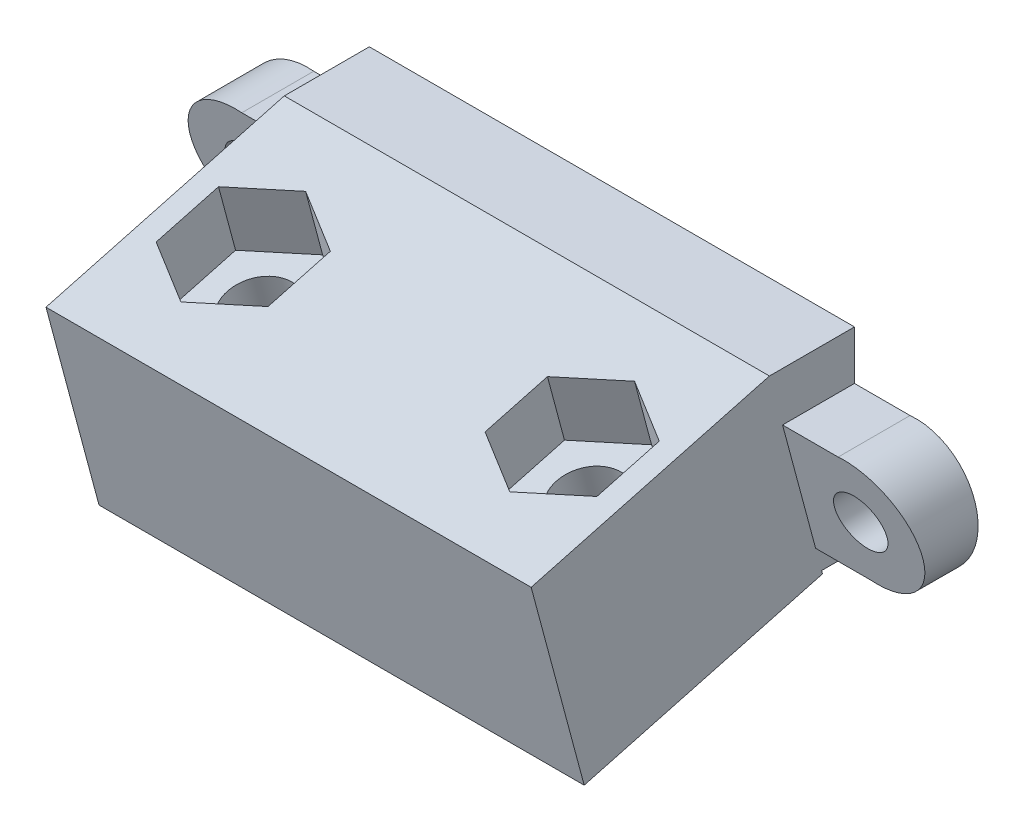
SolidWorks part; units mm, degrees
ref_plane "Front Plane" through (0, 0, 0) normal (0, 0, 1) x (1, 0, 0)
ref_plane "Top Plane" through (0, 0, 0) normal (0, 1, 0) x (1, 0, 0)
ref_plane "Right Plane" through (0, 0, 0) normal (1, 0, 0) x (0, 0, -1)
sketch "Sketch1" plane through (0, 0, 0) normal (0, 0, 1) x (1, 0, 0)
  line L0 (0, 2.5231) -> (3.38, 2.5231) construction
  line L1 (-32.88, 2.5231) -> (-29.5, 2.5231) construction
  line L2 (-32.88, 10.0231) -> (-29.5, 10.0231)
  line L3 (-29.5, 10.0231) -> (-29.5, 13)
  line L4 (-29.5, 13) -> (0, 13)
  line L5 (0, 13) -> (0, 10.0231)
  line L6 (0, 10.0231) -> (3.38, 10.0231)
  line L7 (3.38, 2.5231) -> (0, 2.5231)
  line L8 (0, 2.5231) -> (0, 1.1677)
  line L9 (0, 1.1677) -> (-29.5, 1.1677)
  line L10 (-29.5, 1.1677) -> (-29.5, 2.5231)
  line L11 (-29.5, 2.5231) -> (-32.88, 2.5231)
  line L12 (10.8, 1.1677) -> (-39.2, 1.1677) construction
  circle A0 centre (-33.25, 6.2731) radius 1.6
  circle A1 centre (3.75, 6.2731) radius 1.6
  arc A2 (3.38, 10.0231) -> (3.38, 2.5231) centre (3.75, 6.2731) cw
  arc A3 (-32.88, 10.0231) -> (-32.88, 2.5231) centre (-33.25, 6.2731) ccw
  circle A4 centre (-33.25, 6.2731) radius 1.6 construction
  circle A5 centre (3.75, 6.2731) radius 1.6 construction
  dimension "D1" = 0
extrude "Boss-Extrude1" add sketch "Sketch1" along normal blind 2
sketch "Sketch3" plane through (0, 1.3876, 0.3718) normal (0, 0.9659, 0.2588) x (1, 0, 0)
  line L0 (-29.5, -1.6296) -> (0, -1.6296) construction
  line L1 (0, -1.6296) -> (-29.5, -1.6296)
  line L2 (0, -1.6296) -> (0, -16.6296)
  line L3 (0, -16.6296) -> (-29.5, -16.6296)
  line L4 (-29.5, -1.6296) -> (-29.5, -16.6296)
  line L5 (0, -1.6296) -> (-29.5, -16.6296) construction
  line L6 (0, -16.6296) -> (-29.5, -1.6296) construction
  line L7 (-29.5, -1.2788) -> (-29.5, -1.6296) construction
  circle A0 centre (-4.75, -9.1296) radius 2
  circle A1 centre (-24.75, -9.1296) radius 2
  point P4 (-14.75, -9.1296)
  dimension "D4" = 4
  dimension "D7" = 4
  dimension "D1" = 15
  dimension "D2" = 20
  dimension "D3" = 4.75
  dimension "D5" = 7.5
  dimension "D6" = 7.5
extrude "Boss-Extrude2" add sketch "Sketch3" along normal up to vertex (11.6382 mm away) separate body up to point (-29.5, 13, 2)
extrude "Boss-Extrude3" add sketch "Sketch1<2>" along normal up to surface (3.368 mm away) up to face at (-14.75, 6.5866, 3.452)
sketch "Sketch1<2>" plane through (0, 0, 0) normal (0, 0, 1) x (1, 0, 0) same geometry as "Sketch1"
extrude "Boss-Extrude4" add sketch "Sketch3<2>" along normal up to vertex (12.4587 mm away) up to point (-29.5, 13, 5.1704)
sketch "Sketch3<2>" plane through (0, 1.3876, 0.3718) normal (0, 0.9659, 0.2588) x (1, 0, 0) same geometry as "Sketch3"
sketch "Sketch4" plane through (0, 13.4218, 3.5964) normal (0, 0.9659, 0.2588) x (1, 0, 0)
  line L1 (-1.35, -11.0926) -> (-1.35, -7.1666)
  line L2 (-1.35, -7.1666) -> (-4.75, -5.2036)
  line L3 (-4.75, -5.2036) -> (-8.15, -7.1666)
  line L4 (-8.15, -7.1666) -> (-8.15, -11.0926)
  line L5 (-8.15, -11.0926) -> (-4.75, -13.0556)
  line L6 (-4.75, -13.0556) -> (-1.35, -11.0926)
  line L7 (-21.35, -7.1666) -> (-24.75, -5.2036)
  line L8 (-24.75, -5.2036) -> (-28.15, -7.1666)
  line L9 (-28.15, -7.1666) -> (-28.15, -11.0926)
  line L10 (-28.15, -11.0926) -> (-24.75, -13.0556)
  line L11 (-24.75, -13.0556) -> (-21.35, -11.0926)
  line L12 (-21.35, -11.0926) -> (-21.35, -7.1666)
  circle A0 centre (-4.75, -9.1296) radius 3.4 construction
  circle A1 centre (-24.75, -9.1296) radius 3.4 construction
  dimension "D1" = 6.8
  dimension "D2" = 6.8
extrude "Cut-Extrude1" cut sketch "Sketch4" against normal blind 4
